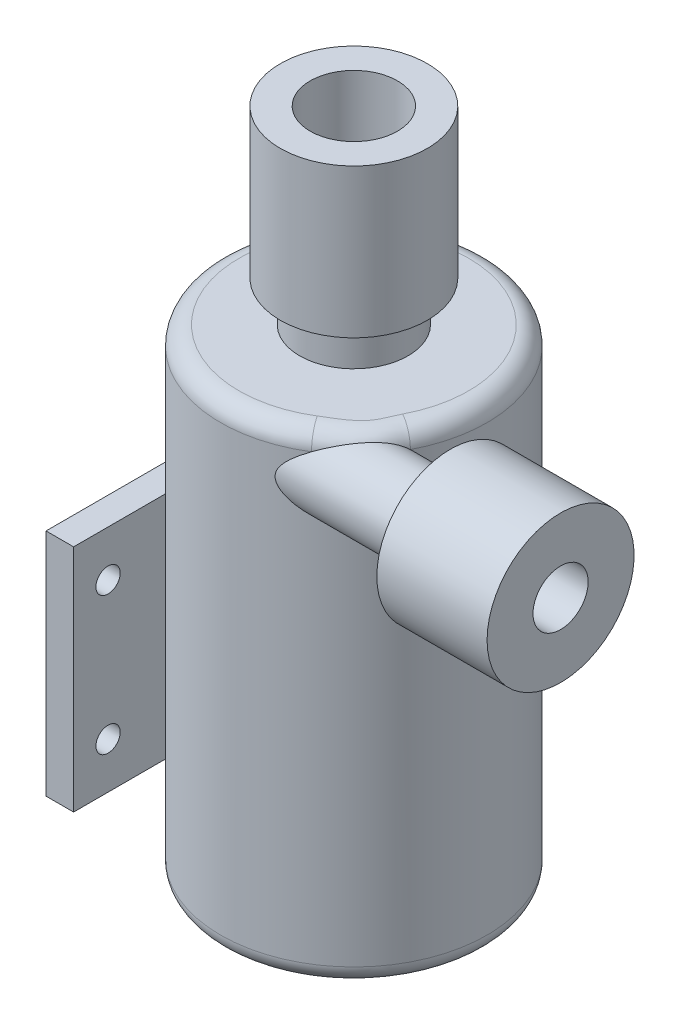
SolidWorks part; units mm, degrees
material "Delrin 2700 NC010, Low Viscosity Acetal Copolymer (SS)"
ref_plane "Front" through (0, 0, 0) normal (0, 0, 1) x (1, 0, 0)
ref_plane "Top" through (0, 0, 0) normal (0, 1, 0) x (1, 0, 0)
ref_plane "Right" through (0, 0, 0) normal (1, 0, 0) x (0, 0, -1)
sketch "Sketch1" plane through (0, 0, 0) normal (0, 1, 0) x (1, 0, 0)
  circle A0 centre (0, 0) radius 18.415
  dimension "D1" = 36.83
extrude "Boss-Extrude1" add sketch "Sketch1" along normal blind 66.421
sketch "Sketch2" plane through (0, 66.421, 0) normal (0, 1, 0) x (1, 0, 0)
  circle A0 centre (0, 0) radius 7.493
  dimension "D1" = 14.986
extrude "Boss-Extrude2" add sketch "Sketch2" along normal blind 5.588
sketch "Sketch3" plane through (0, 72.009, 0) normal (0, 1, 0) x (1, 0, 0)
  circle A0 centre (0, 0) radius 10.16
  circle A1 centre (0, 0) radius 6.0325
  dimension "D1" = 20.32
  dimension "D2" = 12.065
extrude "Boss-Extrude3" add sketch "Sketch3" along normal blind 20.574
sketch "Sketch4" plane through (0, 0, 0) normal (1, 0, 0) x (0, 0, -1)
  line L0 (18.415, 66.421) -> (-18.415, 66.421) construction
  line L1 (-18.415, 66.421) -> (-18.415, 0) construction
  circle A0 centre (-12.065, 60.071) radius 5.207
  dimension "D1" = 10.414
  dimension "D2" = 6.35
  dimension "D3" = 6.35
extrude "Boss-Extrude4" add sketch "Sketch4" along normal blind 25.4
sketch "Sketch5" plane through (25.4, 0, 0) normal (1, 0, 0) x (0, 0, -1)
  circle A0 centre (-12.065, 60.071) radius 10.16
  circle A1 centre (-12.065, 60.071) radius 3.81
  dimension "D1" = 20.32
  dimension "D2" = 7.62
extrude "Boss-Extrude5" add sketch "Sketch5" along normal blind 15.24
sketch "Sketch6" plane through (0, 0, 0) normal (1, 0, 0) x (0, 0, -1)
  line L0 (0, 0) -> (0, 26.797) construction
  line L1 (-18.415, 0) -> (18.415, 0) construction
  line L2 (-22.225, 42.672) -> (22.225, 42.672)
  line L3 (-22.225, 42.672) -> (-22.225, 10.922)
  line L4 (-22.225, 10.922) -> (22.225, 10.922)
  line L5 (22.225, 42.672) -> (22.225, 10.922)
  line L6 (-22.225, 42.672) -> (22.225, 10.922) construction
  line L7 (-22.225, 10.922) -> (22.225, 42.672) construction
  line L9 (-17.4625, 36.322) -> (17.4625, 36.322) construction
  line L10 (-17.4625, 36.322) -> (-17.4625, 17.272) construction
  line L11 (-17.4625, 17.272) -> (17.4625, 17.272) construction
  line L12 (17.4625, 36.322) -> (17.4625, 17.272) construction
  line L13 (-17.4625, 36.322) -> (17.4625, 17.272) construction
  line L14 (-17.4625, 17.272) -> (17.4625, 36.322) construction
  circle A0 centre (-17.4625, 36.322) radius 1.6764
  circle A1 centre (17.4625, 36.322) radius 1.6764
  circle A2 centre (17.4625, 17.272) radius 1.6764
  circle A3 centre (-17.4625, 17.272) radius 1.6764
  dimension "D4" = 3.3528
  dimension "D1" = 44.45
  dimension "D2" = 31.75
  dimension "D3" = 10.922
  dimension "D5" = 34.925
  dimension "D6" = 19.05
extrude "Boss-Extrude6" add sketch "Sketch6" along normal blind 3.81 from offset 20.32 offset against normal yes
fillet "Fillet1" radius 2.54 2 edges at (0, 66.421, 18.415) (0, 0, 18.415)
